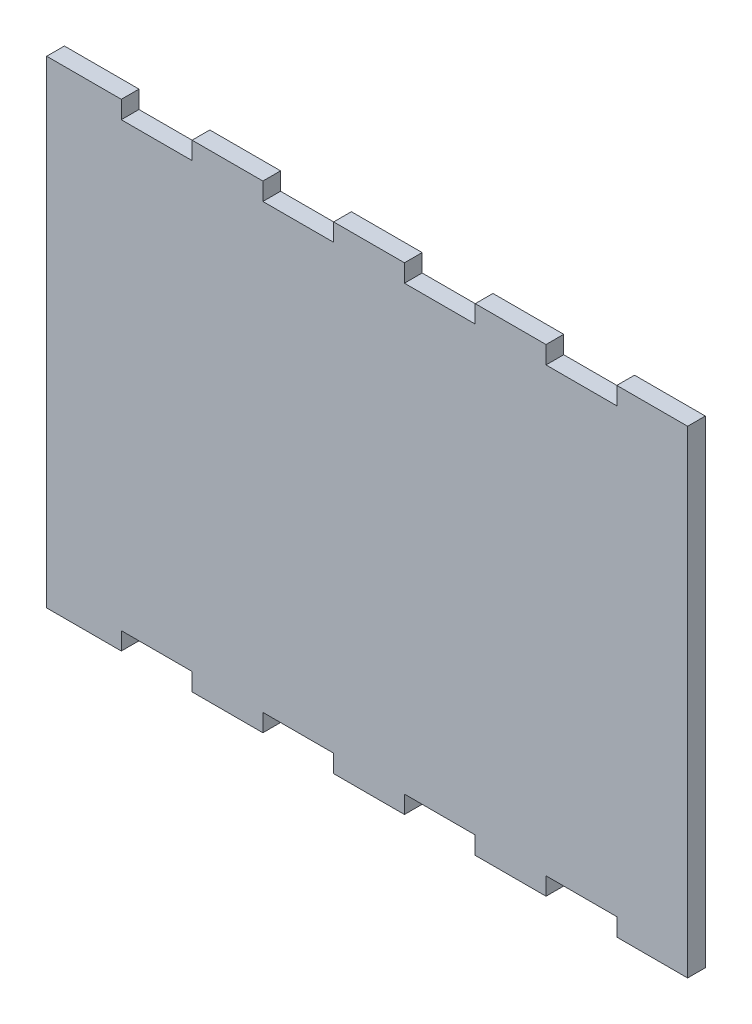
SolidWorks part; units mm, degrees
ref_plane "Front Plane" through (0, 0, 0) normal (0, 0, 1) x (1, 0, 0)
ref_plane "Top Plane" through (0, 0, 0) normal (0, 1, 0) x (1, 0, 0)
ref_plane "Right Plane" through (0, 0, 0) normal (1, 0, 0) x (0, 0, -1)
sketch "Sketch1" plane through (0, 0, 0) normal (0, 0, 1) x (1, 0, 0)
  line L1 (90.6195, 155.575) -> (-139.3499, 155.575)
  line L2 (90.6195, 155.575) -> (90.6195, -15.875)
  line L3 (90.6195, -15.875) -> (-139.3499, -15.875)
  line L4 (-139.3499, 155.575) -> (-139.3499, -15.875)
extrude "Boss-Extrude1" add sketch "Sketch1" along normal blind 6.35
sketch "Sketch2" plane through (0, 0, 6.35) normal (0, 0, 1) x (1, 0, 0)
  line L0 (-139.3499, -15.875) -> (90.6195, -15.875) construction
  line L1 (-112.5805, -9.525) -> (-87.1805, -9.525)
  line L2 (-112.5805, -9.525) -> (-112.5805, -15.875)
  line L3 (-112.5805, -15.875) -> (-87.1805, -15.875)
  line L4 (-87.1805, -9.525) -> (-87.1805, -15.875)
  line L5 (-87.1805, -9.525) -> (-87.1805, -15.875) construction
  line L6 (90.6195, 155.575) -> (-139.3499, 155.575) construction
  line L7 (-112.5805, 149.225) -> (-87.1805, 149.225)
  line L8 (-112.5805, 149.225) -> (-112.5805, 155.575)
  line L9 (-112.5805, 155.575) -> (-87.1805, 155.575)
  line L10 (-87.1805, 149.225) -> (-87.1805, 155.575)
  line L11 (-87.1805, 149.225) -> (-87.1805, 155.575) construction
extrude "Cut-Extrude1" cut sketch "Sketch2" against normal blind 6.35
pattern_linear "LPattern1" count 4 spacing 50.8 along (1, 0, 0) of "Cut-Extrude1"
